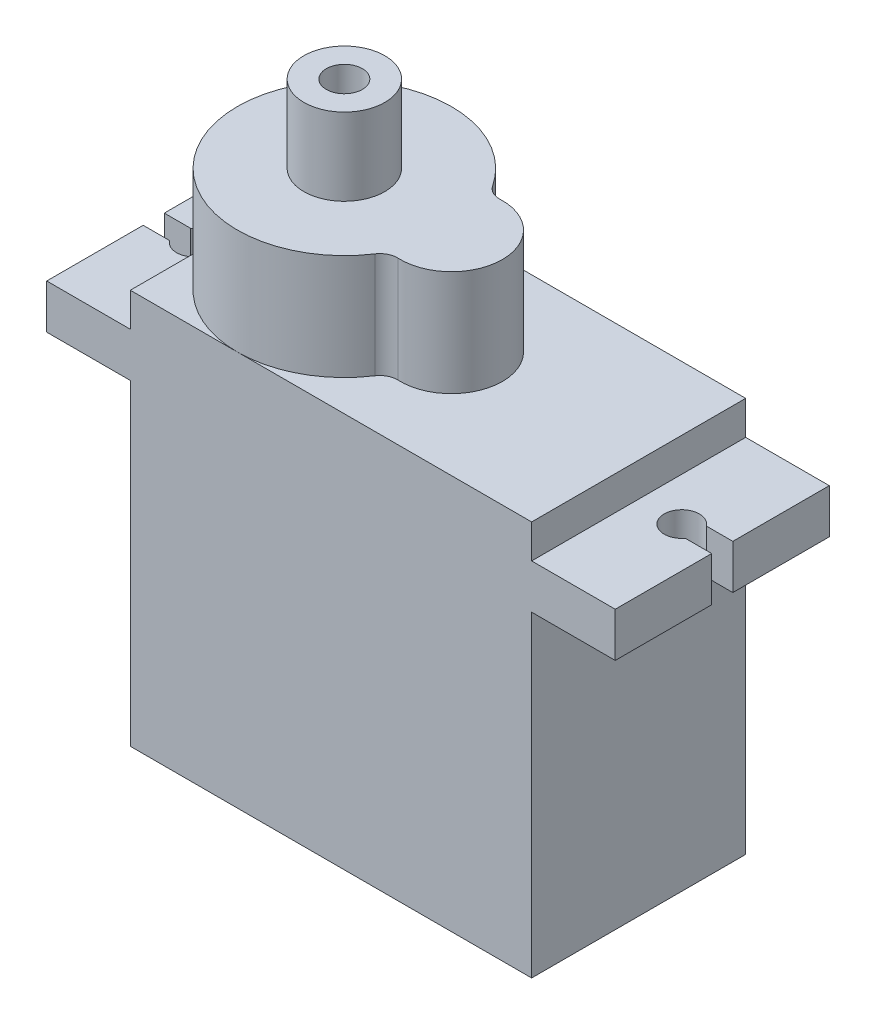
SolidWorks part; units mm, degrees
material "CA"
ref_plane "前视基准面" through (0, 0, 0) normal (0, 0, 1) x (1, 0, 0)
ref_plane "上视基准面" through (0, 0, 0) normal (0, 1, 0) x (1, 0, 0)
ref_plane "右视基准面" through (0, 0, 0) normal (1, 0, 0) x (0, 0, -1)
other "Configuration Table"
sketch "草图1" plane through (0, 0, 0) normal (0, 1, 0) x (1, 0, 0)
  line L1 (-11.4, 6.08) -> (11.4, 6.08)
  line L2 (-11.4, 6.08) -> (-11.4, -6.08)
  line L3 (-11.4, -6.08) -> (11.4, -6.08)
  line L4 (11.4, 6.08) -> (11.4, -6.08)
  line L5 (-11.4, 6.08) -> (11.4, -6.08) construction
  line L6 (-11.4, -6.08) -> (11.4, 6.08) construction
  point P0 (0, 0)
  dimension "D1" = 22.8
  dimension "D2" = 12.16
extrude "凸台-拉伸1" add sketch "草图1" along normal blind 22.44
sketch "草图3" plane through (0, 0, 0) normal (0, 1, 0) x (1, 0, 0)
  line L0 (11.4, 6.08) -> (-11.4, 6.08) construction
  line L1 (16.15, -6.08) -> (-16.15, -6.08)
  line L2 (16.15, -6.08) -> (16.15, 6.08)
  line L3 (16.15, 6.08) -> (-16.15, 6.08)
  line L4 (-16.15, -6.08) -> (-16.15, 6.08)
  line L5 (16.15, -6.08) -> (-16.15, 6.08) construction
  line L6 (16.15, 6.08) -> (-16.15, -6.08) construction
  point P0 (0, 0)
  dimension "D1" = 32.3
extrude "凸台-拉伸2" add sketch "草图3" along normal blind 2.52 from offset 18
sketch "草图4" plane through (0, 22.44, 0) normal (0, 1, 0) x (1, 0, 0)
  line L0 (11.4, 6.08) -> (-11.4, 6.08) construction
  line L1 (-11.4, 6.08) -> (-11.4, -6.08) construction
  line L2 (-11.4, -6.08) -> (11.4, -6.08) construction
  circle A0 centre (-5.32, 0) radius 6.08
  circle A3 centre (0.76, 0) radius 2.9
  dimension "D1" = 5.8
extrude "凸台-拉伸3" add sketch "草图4" along normal blind 6 contours A3 A0 | A0 A3 | A0 A3 region at (-0.5867, 22.44, 0) region at (1.8578, 22.44, 0) region at (-5.8586, 22.44, 0)
fillet "圆角1" radius 1 2 edges at (0.0684, 25.44, -2.8163) (0.0684, 25.44, 2.8163)
sketch "草图5" plane through (0, 20.52, 0) normal (0, 1, 0) x (1, 0, 0)
  line L0 (0, 9.4098) -> (0, -9.6873) construction
  line L1 (-16.15, 6.08) -> (-16.15, -6.08) construction
  line L2 (-18.45, 0.6) -> (-13.85, 0.6)
  line L3 (-18.45, 0.6) -> (-18.45, -0.6)
  line L4 (-18.45, -0.6) -> (-13.85, -0.6)
  line L5 (-13.85, 0.6) -> (-13.85, -0.6)
  line L6 (-18.45, 0.6) -> (-13.85, -0.6) construction
  line L7 (-18.45, -0.6) -> (-13.85, 0.6) construction
  line L12 (18.45, -0.6) -> (13.85, -0.6)
  line L13 (13.85, 0.6) -> (13.85, -0.6)
  line L14 (18.45, 0.6) -> (13.85, 0.6)
  line L15 (18.45, 0.6) -> (18.45, -0.6)
  circle A0 centre (-13.85, 0) radius 1
  circle A1 centre (13.85, 0) radius 1
  point P8 (-16.15, 0)
  line M14 (-16.15, 6.08) -> (-16.15, -6.08)
  dimension "D2" = 2
  dimension "D1" = 27.7
  dimension "D3" = 1.2
extrude "切除-拉伸1" cut sketch "草图5" against normal up to next contours L3 L4 L2 M14 | A0 L2 L4 M14 | L2 A0 L4 L5 | L4 A0 L2 L5 | L14 A1 L12 L13 | L12 A1 L14 L13 | A1 L12 L15 L14 region at (-17.3, 20.52, 0) region at (-15.4669, 20.52, 0) region at (-13.5884, 20.52, 0) region at (-14.32, 20.52, 0) region at (16.6177, 20.52, 0) region at (13.5884, 20.52, 0) region at (14.32, 20.52, 0)
sketch "草图6" plane through (0, 28.44, 0) normal (0, 1, 0) x (1, 0, 0)
  circle A0 centre (-5.32, 0) radius 2.3
  arc A1 (-0.2435, 3.346) -> (-0.2435, -3.346) centre (-5.32, 0) ccw construction
  dimension "D1" = 4.6
extrude "凸台-拉伸4" add sketch "草图6" along normal blind 4.39 contours A0
hole_wizard "M2.5 螺纹孔1" positions "草图8" profile "草图9" tap size "M2.5" standard "GB"
sketch "草图8" plane through (0, 32.83, 0) normal (0, 1, 0) x (1, 0, 0)
  point P0 (-5.32, 0)
cosmetic thread "孔螺蚊线1" parameters "D1"=5, "D2"=2.5
sketch "草图9" plane through (-5.32, 32.83, 0) normal (1, 0, 0) x (0, 0, 1)
  line L0 (0, 0) -> (0, 5.0059)
  line L1 (0, 5.0059) -> (1.025, 4.39)
  line L2 (1.025, 4.39) -> (1.025, 0)
  line L5 (1.025, 0) -> (0, 0)
  line L10 (0, 5.0059) -> (-1.025, 4.39) construction
  line L11 (0, -6.35) -> (0, 107.95) construction
  dimension "螺纹孔钻头直径" = 2.05
  dimension "螺纹孔钻头深度" = 4.39
  dimension "导头角度" = 118
sketch "草图10" plane through (-11.4, 0, 0) normal (-1, 0, 0) x (0, 0, 1)
  line L0 (-6.08, 0) -> (6.08, 0) construction
  line L1 (-1.8, 5.58) -> (1.8, 5.58)
  line L2 (-1.8, 5.58) -> (-1.8, 4.28)
  line L3 (-1.8, 4.28) -> (1.8, 4.28)
  line L4 (1.8, 5.58) -> (1.8, 4.28)
  line L5 (-1.8, 5.58) -> (1.8, 4.28) construction
  line L6 (-1.8, 4.28) -> (1.8, 5.58) construction
  point P0 (0, 4.93)
  point P7 (0, 0)
  dimension "D1" = 5.58
  dimension "D2" = 1.3
  dimension "D3" = 3.6
extrude "凸台-拉伸5" add sketch "草图10" along normal blind 2
